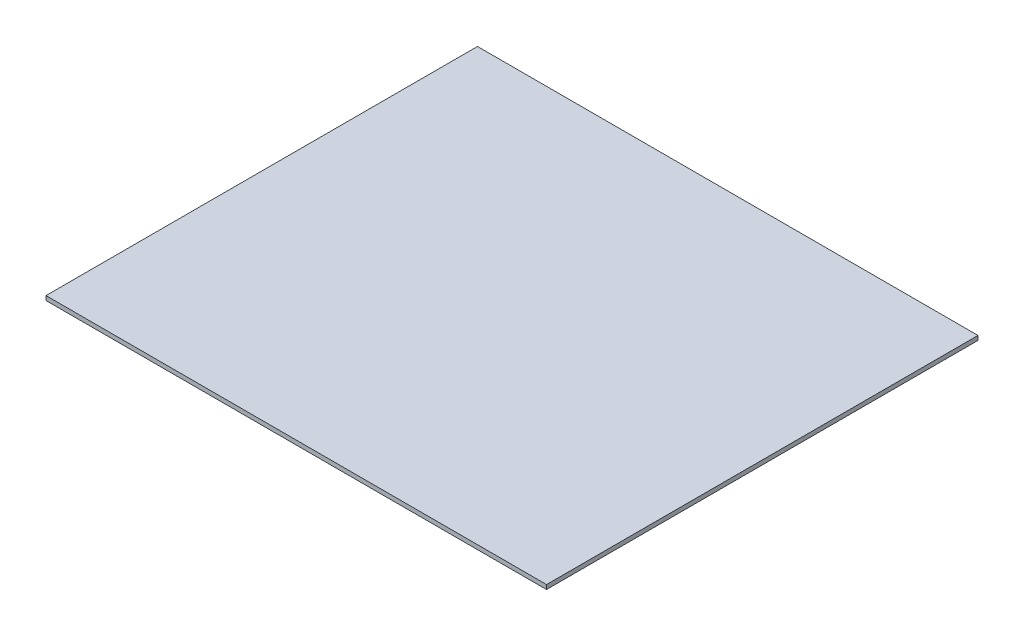
SolidWorks part; units mm, degrees
material "Acrylic (Medium-high impact)"
ref_plane "Front Plane" through (0, 0, 0) normal (0, 0, 1) x (1, 0, 0)
ref_plane "Top Plane" through (0, 0, 0) normal (0, 1, 0) x (1, 0, 0)
ref_plane "Right Plane" through (0, 0, 0) normal (1, 0, 0) x (0, 0, -1)
sketch "Sketch1" plane through (0, 0, 0) normal (0, 1, 0) x (1, 0, 0)
  line L1 (-184.15, -158.75) -> (184.15, -158.75)
  line L2 (-184.15, -158.75) -> (-184.15, 158.75)
  line L3 (-184.15, 158.75) -> (184.15, 158.75)
  line L4 (184.15, -158.75) -> (184.15, 158.75)
  line L5 (-184.15, -158.75) -> (184.15, 158.75) construction
  line L6 (-184.15, 158.75) -> (184.15, -158.75) construction
  point P0 (0, 0)
  dimension "D1" = 317.5
  dimension "D2" = 368.3
extrude "Boss-Extrude1" add sketch "Sketch1" along normal blind 3.175
